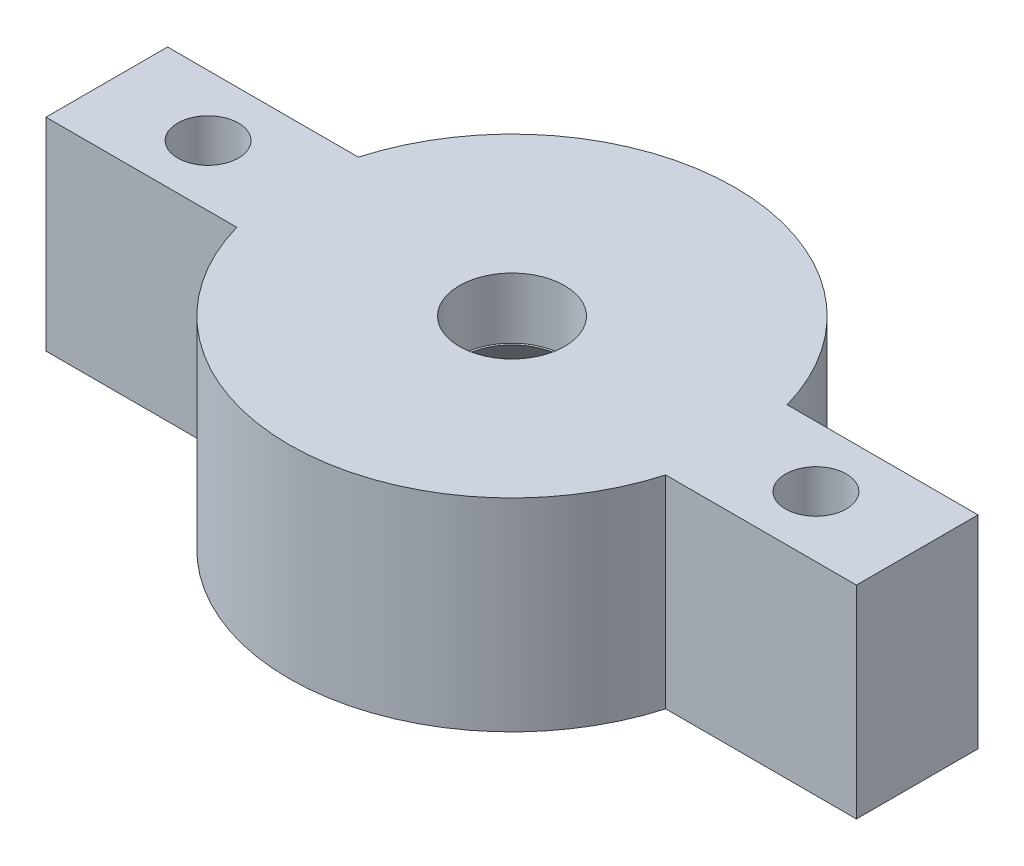
SolidWorks part; units mm, degrees
ref_plane "Front Plane" through (0, 0, 0) normal (0, 0, 1) x (1, 0, 0)
ref_plane "Top Plane" through (0, 0, 0) normal (0, 1, 0) x (1, 0, 0)
ref_plane "Right Plane" through (0, 0, 0) normal (1, 0, 0) x (0, 0, -1)
sketch "Sketch2" plane through (0, 0, 0) normal (1, 0, 0) x (0, 0, -1)
  line L1 (-3, -5) -> (3, -5)
  line L2 (-3, -5) -> (-3, 5)
  line L3 (-3, 5) -> (3, 5)
  line L4 (3, -5) -> (3, 5)
  line L5 (-3, -5) -> (3, 5) construction
  line L6 (-3, 5) -> (3, -5) construction
  point P0 (0, 0)
  dimension "D1" = 6
  dimension "D2" = 10
extrude "Boss-Extrude1" add sketch "Sketch2" along normal blind 40
sketch "Sketch3" plane through (0, 5, 0) normal (0, 1, 0) x (1, 0, 0)
  line L0 (0, 0) -> (40, 0) construction
  line L1 (40, 3) -> (40, -3) construction
  circle A0 centre (20, 0) radius 11
  dimension "D1" = 22
extrude "Boss-Extrude2" add sketch "Sketch3" against normal up to surface (10 mm away) up to face at (20, -5, 0)
sketch "Sketch4" plane through (0, -5, 0) normal (0, -1, 0) x (-1, 0, 0)
  circle A0 centre (-20, 0) radius 7.5
  circle A1 centre (-20, 0) radius 11 construction
  dimension "D1" = 15
extrude "Cut-Extrude1" cut sketch "Sketch4" against normal blind 2
sketch "Sketch5" plane through (0, 0, 0) normal (0, 0, -1) x (-1, 0, 0)
  line L0 (-20, -3) -> (-27.5, -3)
  line L2 (-27.5, -3) -> (-22.5, 2)
  line L3 (-22.5, 2) -> (-20, 2)
  line L5 (-20, 2) -> (-20, -3)
  line L6 (-30.583, -5) -> (-9.417, -5) construction
  line L7 (-9.417, 5) -> (-30.583, 5) construction
  point P10 (-20, 5)
  dimension "D1" = 2
  dimension "D2" = 7.5
  dimension "D3" = 2.5
  dimension "D4" = 5
revolve "Cut-Revolve1" cut sketch "Sketch5" angle 360 about L5
sketch "Sketch6" plane through (0, 2, 0) normal (0, -1, 0) x (1, 0, 0)
  circle A0 centre (20, 0) radius 2.6
  circle A1 centre (20, 0) radius 2.5
  circle A2 centre (20, 0) radius 2.5 construction
  dimension "D2" = 0.1
  dimension "D1" = 0
extrude "Cut-Extrude2" cut sketch "Sketch6" against normal blind 13
fillet "Fillet1" radius 2 1 edges at (20, -5, -7.5)
sketch "Sketch7" plane through (0, -5, 0) normal (0, -1, 0) x (1, 0, 0)
  line L0 (0, 3) -> (0, -3) construction
  line L1 (20, 11) -> (20, -11) construction
  circle A0 centre (5, 0) radius 1.5
  arc A1 (30.583, 3) -> (9.417, 3) centre (20, 0) ccw construction
  arc A2 (9.417, -3) -> (30.583, -3) centre (20, 0) ccw construction
  circle A3 centre (35, 0) radius 1.5
  dimension "D1" = 3
  dimension "D2" = 5
extrude "Cut-Extrude3" cut sketch "Sketch7" against normal up to next
